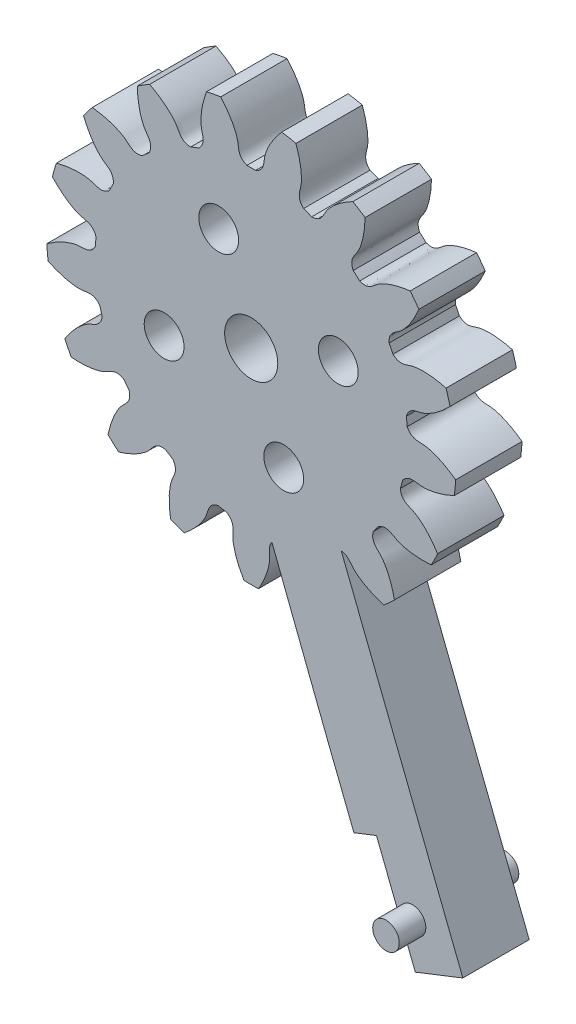
SolidWorks part; units mm, degrees
material "45"
ref_plane "前视基准面" through (0, 0, 0) normal (0, 0, 1) x (1, 0, 0)
ref_plane "上视基准面" through (0, 0, 0) normal (0, 1, 0) x (1, 0, 0)
ref_plane "右视基准面" through (0, 0, 0) normal (1, 0, 0) x (0, 0, -1)
sketch "草图1" plane through (0, 0, 0) normal (0, 0, 1) x (1, 0, 0)
  circle A0 centre (0, 0) radius 15.4185
extrude "凸台-拉伸1" add sketch "草图1" along normal blind 5
ref_axis "基准轴1" through (0, 0, 5) along (0, 0, -1)
sketch "草图2" plane through (0, 0, 0) normal (0, 0, 1) x (1, 0, 0)
  line L0 (0, 0) -> (0, 15.4185) construction
  circle A0 centre (0, 0) radius 15.4185 construction
  arc A1 (0.3273, 11.7622) -> (-0.3273, 11.7622) centre (0, 0) ccw
  arc A2 (5.0567, 17.4322) -> (-5.0567, 17.4322) centre (0, 0) ccw
  spline S0 degree 3 poles (0.3273, 11.7622) (1.019, 12.0505) (0.9189, 12.5861) (1.036, 13.0892) (1.0468, 13.1319) (1.0598, 13.1794) (1.0753, 13.2316) (1.0934, 13.2885) (1.1143, 13.3498) (1.1382, 13.4156) (1.1652, 13.4858) (1.1956, 13.5602) (1.2296, 13.6388) (1.2672, 13.7213) (1.3088, 13.8078) (1.3544, 13.898) (1.4042, 13.9919) (1.4584, 14.0894) (1.5172, 14.1902) (1.5807, 14.2942) (1.649, 14.4013) (1.7223, 14.5113) (1.8008, 14.6242) (1.8846, 14.7396) (1.9737, 14.8574) (2.0685, 14.9775) (2.1689, 15.0997) (2.2751, 15.2239) (2.3872, 15.3497) (2.5053, 15.4771) (2.6296, 15.6058) (2.7601, 15.7356) (2.8969, 15.8665) (3.0401, 15.998) (3.1898, 16.1301) (3.346, 16.2625) (3.5089, 16.3951) (3.6785, 16.5276) (3.8549, 16.6597) (4.0381, 16.7913) (4.2282, 16.9222) (4.4251, 17.0521) (4.6999, 17.2256) (4.9121, 17.3507) (5.0567, 17.4322) knots 0 0 0 0 0.193883 0.199024 0.204851 0.211363 0.21856 0.226443 0.235011 0.244265 0.254205 0.264829 0.27614 0.288136 0.300817 0.314184 0.328236 0.342973 0.358397 0.374505 0.391299 0.408779 0.426944 0.445795 0.465331 0.485552 0.506459 0.528051 0.550329 0.573293 0.596941 0.621276 0.646296 0.672001 0.698392 0.725468 0.753229 0.781677 0.810809 0.840627 0.871131 0.90232 0.934195 1 1 1 1
  spline S1 degree 3 poles (-0.3273, 11.7622) (-1.019, 12.0505) (-0.9189, 12.5861) (-1.036, 13.0892) (-1.0468, 13.1319) (-1.0598, 13.1794) (-1.0753, 13.2316) (-1.0934, 13.2885) (-1.1143, 13.3498) (-1.1382, 13.4156) (-1.1652, 13.4858) (-1.1956, 13.5602) (-1.2296, 13.6388) (-1.2672, 13.7213) (-1.3088, 13.8078) (-1.3544, 13.898) (-1.4042, 13.9919) (-1.4584, 14.0894) (-1.5172, 14.1902) (-1.5807, 14.2942) (-1.649, 14.4013) (-1.7223, 14.5113) (-1.8008, 14.6242) (-1.8846, 14.7396) (-1.9737, 14.8574) (-2.0685, 14.9775) (-2.1689, 15.0997) (-2.2751, 15.2239) (-2.3872, 15.3497) (-2.5053, 15.4771) (-2.6296, 15.6058) (-2.7601, 15.7356) (-2.8969, 15.8665) (-3.0401, 15.998) (-3.1898, 16.1301) (-3.346, 16.2625) (-3.5089, 16.3951) (-3.6785, 16.5276) (-3.8549, 16.6597) (-4.0381, 16.7913) (-4.2282, 16.9222) (-4.4251, 17.0521) (-4.6999, 17.2256) (-4.9121, 17.3507) (-5.0567, 17.4322) knots 0 0 0 0 0.193883 0.199024 0.204851 0.211363 0.21856 0.226443 0.235011 0.244265 0.254205 0.264829 0.27614 0.288136 0.300817 0.314184 0.328236 0.342973 0.358397 0.374505 0.391299 0.408779 0.426944 0.445795 0.465331 0.485552 0.506459 0.528051 0.550329 0.573293 0.596941 0.621276 0.646296 0.672001 0.698392 0.725468 0.753229 0.781677 0.810809 0.840627 0.871131 0.90232 0.934195 1 1 1 1
extrude "切除-拉伸1" cut sketch "草图2" along normal through all
pattern_circular "阵列(圆周)1" count 17 over 360 about axis through (0, 0, 5) along (0, 0, -1) of "切除-拉伸1"
sketch "草图3" plane through (0, 0, 0) normal (0, 0, 1) x (1, 0, 0)
  circle A0 centre (0, 0) radius 13.7955 construction
  dimension "Dn" = 27.591
sketch "草图4" plane through (0, 0, 5) normal (0, 0, 1) x (1, 0, 0)
  circle A0 centre (0, 0) radius 2
  dimension "D1" = 4
extrude "切除-拉伸2" cut sketch "草图4" against normal blind 10
sketch "草图11" plane through (0, 0, 0) normal (0, 0, -1) x (-1, 0, 0)
  line L3 (0, 0) -> (-5.5698, -14.3773) construction
  line L4 (-10.9285, -20.367) -> (-5.6495, -6.9382)
  line L6 (-10.9285, -20.367) -> (-16.843, -35.4124)
  line L7 (-16.843, -35.4124) -> (-11.5697, -37.4854)
  line L8 (-11.5697, -37.4854) -> (-5.6449, -22.4139)
  line L18 (-5.6495, -6.9382) -> (-0.4992, -8.9334)
  line L25 (-5.6449, -22.4139) -> (-0.4325, -8.9593)
  line L28 (-0.4992, -8.9334) -> (-0.4325, -8.9593)
  arc A0 (-6.0744, -14.1715) -> (-5.0582, -14.5652) centre (0, 0) ccw construction
extrude "凸台-拉伸2" add sketch "草图11" against normal blind 5
sketch "草图15" plane through (0, 0, 0) normal (0, 0, -1) x (-1, 0, 0)
  line L0 (-14.2064, -36.4489) -> (-10.4493, -26.8917) construction
  line L1 (-16.843, -35.4124) -> (-11.5697, -37.4854) construction
  circle A0 centre (-12.1487, -31.2147) radius 1
  dimension "D1" = 5.6241
extrude "凸台-拉伸3" add sketch "草图15" along normal blind 2 and the other way blind 7
sketch "草图16" plane through (-2.7425, -1.0781, 0) normal (-0.9307, -0.3659, 0) x (0, 0, 1)
  line L0 (5, -39.1195) -> (5, -22.9252) construction
  line L1 (0, -39.1195) -> (5, -39.1195)
  line L2 (0, -39.1195) -> (0, -36.6338)
  line L3 (0, -36.6338) -> (5, -36.6338)
  line L4 (5, -39.1195) -> (5, -36.6338)
extrude "切除-拉伸3" cut sketch "草图16" against normal blind 10
sketch "草图17" plane through (0, 0, 0) normal (0, 0, -1) x (-1, 0, 0)
  line L0 (0, 0) -> (2.4487, 6.5577) construction
  circle A0 centre (2.4487, 6.5577) radius 1.5
  circle A1 centre (6.5577, -2.4487) radius 1.5
  circle A2 centre (-2.4487, -6.5577) radius 1.5
  circle A3 centre (-6.5577, 2.4487) radius 1.5
  point P13 (0, 0)
  dimension "D1" = 7
  dimension "D2" = 4
extrude "切除-拉伸4" cut sketch "草图17" against normal blind 10
sketch "草图18" plane through (0, 0, 0) normal (0, 0, -1) x (-1, 0, 0)
  line L0 (-10.6603, -35.1721) -> (-5.6449, -22.4139) construction
  line L1 (-7.7334, -27.7267) -> (-9.43, -27.0598)
  line L2 (-9.43, -27.0598) -> (-12.3569, -34.5051)
  line L3 (-15.9336, -33.0991) -> (-10.6603, -35.1721) construction
  line L4 (-12.3569, -34.5051) -> (-10.6603, -35.1721)
  line L5 (-10.6603, -35.1721) -> (-7.7334, -27.7267)
  dimension "D1" = 8
extrude "切除-拉伸5" cut sketch "草图18" against normal blind 10
